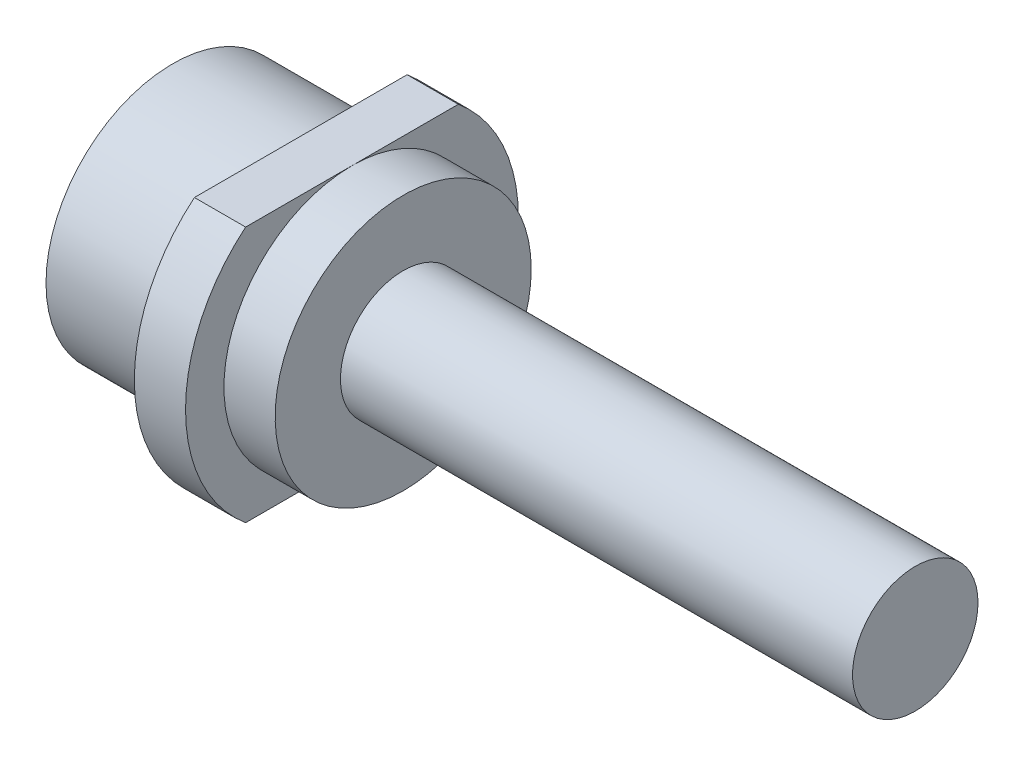
SolidWorks part; units mm, degrees
ref_plane "前视基准面" through (0, 0, 0) normal (0, 0, 1) x (1, 0, 0)
ref_plane "上视基准面" through (0, 0, 0) normal (0, 1, 0) x (1, 0, 0)
ref_plane "右视基准面" through (0, 0, 0) normal (1, 0, 0) x (0, 0, -1)
sketch "草图2" plane through (0, 0, 0) normal (1, 0, 0) x (0, 0, -1)
  line L0 (4.1533, 5) -> (-4.1533, 5)
  line L1 (4.1533, -5) -> (-4.1533, -5)
  arc A0 (-4.1533, 5) -> (-4.1533, -5) centre (0, 0) ccw
  arc A1 (4.1533, -5) -> (4.1533, 5) centre (0, 0) ccw
  dimension "D1" = 13
  dimension "D2" = 10
  dimension "D3" = 5
extrude "凸台-拉伸1" add sketch "草图2" along normal blind 2
sketch "草图3" plane through (2, 0, 0) normal (1, 0, 0) x (0, 0, -1)
  circle A0 centre (0, 0) radius 5
extrude "凸台-拉伸2" add sketch "草图3" along normal blind 2
sketch "草图4" plane through (4, 0, 0) normal (1, 0, 0) x (0, 0, -1)
  circle A0 centre (0, 0) radius 2.45
  dimension "D1" = 4.9
extrude "凸台-拉伸3" add sketch "草图4" along normal blind 20
sketch "草图5" plane through (0, 0, 0) normal (-1, 0, 0) x (0, 0, 1)
  circle A0 centre (0, 0) radius 4.95
extrude "凸台-拉伸4" add sketch "草图5" along normal blind 5
